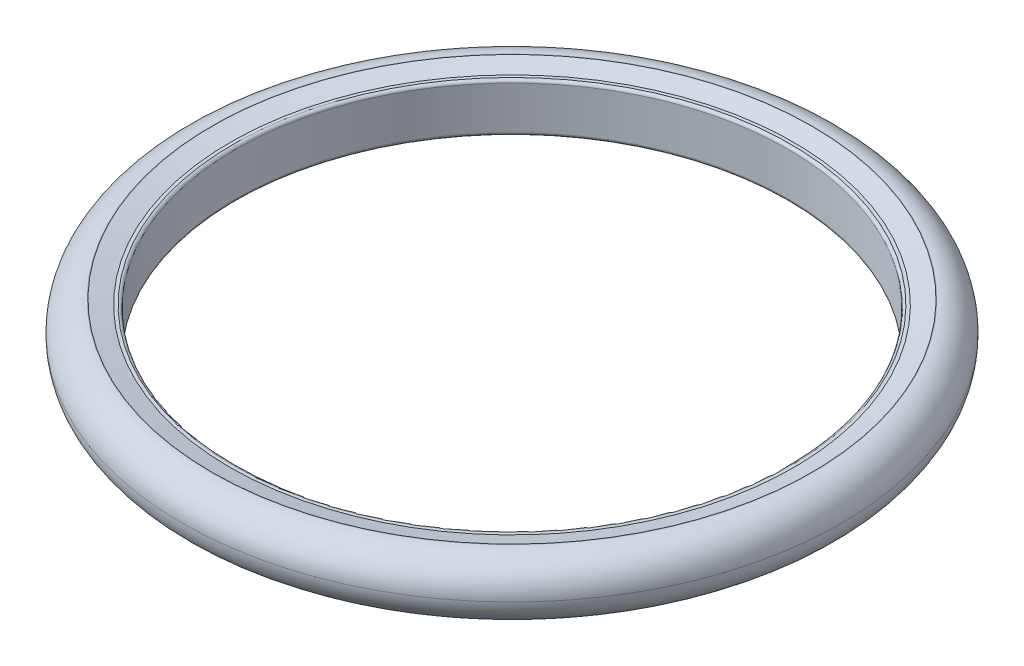
SolidWorks part; units mm, degrees
material "ｴﾁﾚﾝﾌﾟﾛﾋﾟﾚﾝｺﾞﾑ(EPDM) 60 Durometer"
ref_plane "正面" through (0, 0, 0) normal (0, 0, 1) x (1, 0, 0)
ref_plane "平面" through (0, 0, 0) normal (0, 1, 0) x (1, 0, 0)
ref_plane "右側面" through (0, 0, 0) normal (1, 0, 0) x (0, 0, -1)
sketch "ｽｹｯﾁ1" plane through (0, 0, 0) normal (0, 1, 0) x (1, 0, 0)
  circle A0 centre (0, 0) radius 203.2
  circle A1 centre (0, 0) radius 170
  circle A2 centre (0, 0) radius 188.6959
  dimension "D1" = 406.4
  dimension "D2" = 340
extrude "ﾎﾞｽ - 押し出し4" add sketch "ｽｹｯﾁ1" along normal blind 15 contours A2 A1 region at (-183.3587, 0, 0)
extrude "ﾎﾞｽ - 押し出し5" add sketch "ｽｹｯﾁ1<8>" along normal blind 18 contours A0 A2 region at (-197.4526, 0, 0)
sketch "ｽｹｯﾁ1<8>" plane through (0, 0, 0) normal (0, 1, 0) x (1, 0, 0) same geometry as "ｽｹｯﾁ1"
mirror "ﾐﾗｰ1" about plane through (0, 0, 0) normal (0, 1, 0) of "ﾎﾞｽ - 押し出し5", "ﾎﾞｽ - 押し出し4"
chamfer "面取り1" distance 15 angle 15 2 edges at (0, -15, 188.6959) (0, 15, 188.6959) first distance on face at (0, -15, 170) first distance on face at (0, 15, 170)
fillet "ﾌｨﾚｯﾄ1" radius 18 2 edges at (0, 18, 203.2) (0, -18, 203.2)
fillet "ﾌｨﾚｯﾄ2" radius 1.75 2 edges at (0, 15, 170) (0, -15, 170)
